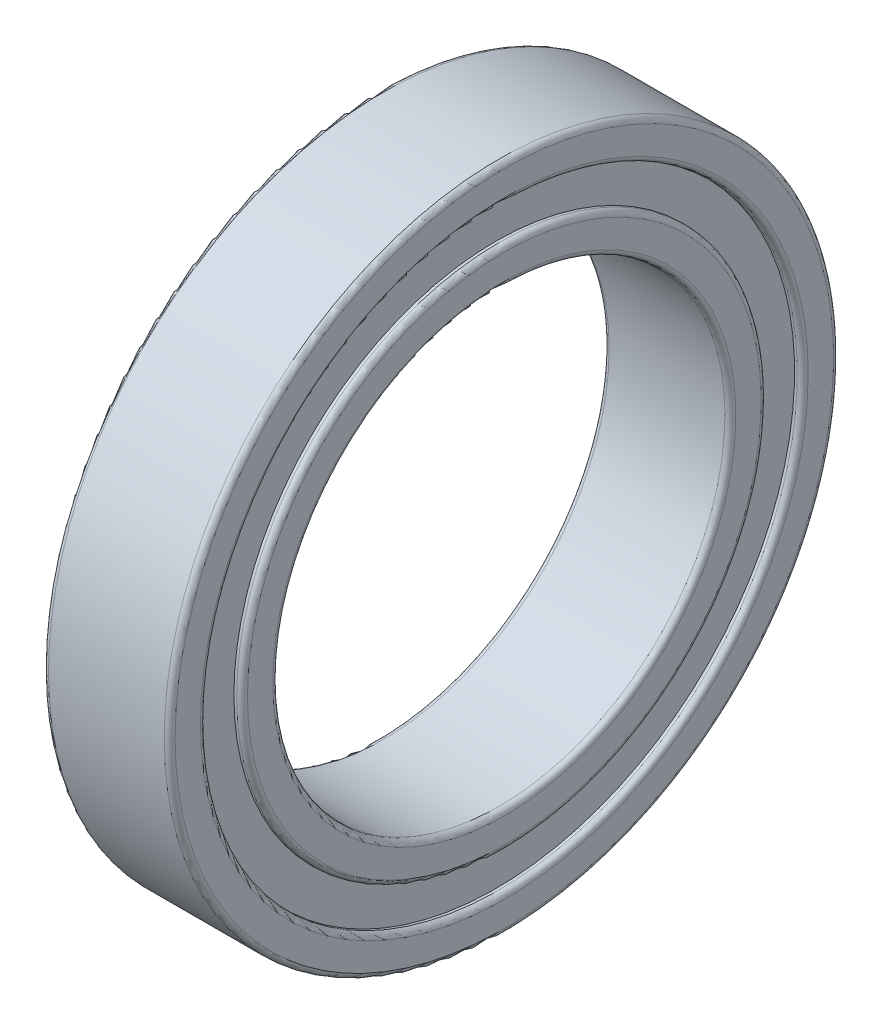
SolidWorks part; units mm, degrees
material "AISI 304"
ref_plane "前视基准面" through (0, 0, 0) normal (0, 0, 1) x (1, 0, 0)
ref_plane "上视基准面" through (0, 0, 0) normal (0, 1, 0) x (1, 0, 0)
ref_plane "右视基准面" through (0, 0, 0) normal (1, 0, 0) x (0, 0, -1)
sketch "尺寸草图" plane through (0, 0, 0) normal (0, 0, 1) x (1, 0, 0)
  line L0 (-19.9271, 0) -> (19.9271, 0) construction
  line L1 (0, 21.603) -> (0, -21.603) construction
  line L2 (-3.2, 18.5) -> (3.2, 18.5)
  line L3 (3.5, 18.2) -> (3.5, 16.8)
  line L4 (-3.5, 18.2) -> (-3.5, 16.8)
  line L5 (-3.2, 16.5) -> (3.2, 16.5)
  line L6 (-3.5, 15.5) -> (3.3577, 15.5) construction
  line L7 (-3.2, 14.5) -> (3.2, 14.5)
  line L8 (3.5, 14.2) -> (3.5, 12.8)
  line L9 (3.2, 12.5) -> (-3.2, 12.5)
  line L10 (-3.5, 12.8) -> (-3.5, 14.2)
  line L11 (0, 15.5) -> (0, 17) construction
  line L13 (2.75, 16.8) -> (3.05, 16.8)
  line L14 (2.75, 16.8) -> (2.75, 14.2)
  line L15 (2.75, 14.2) -> (3.05, 14.2)
  line L16 (3.05, 16.8) -> (3.05, 14.2)
  circle A0 centre (0, 15.5) radius 1.5
  arc A1 (3.5, 16.8) -> (3.2, 16.5) centre (3.2, 16.8) cw
  arc A2 (3.5, 14.2) -> (3.2, 14.5) centre (3.2, 14.2) ccw
  arc A3 (-3.2, 14.5) -> (-3.5, 14.2) centre (-3.2, 14.2) ccw
  arc A4 (-3.2, 16.5) -> (-3.5, 16.8) centre (-3.2, 16.8) cw
  arc A5 (-3.2, 12.5) -> (-3.5, 12.8) centre (-3.2, 12.8) cw
  arc A6 (3.2, 12.5) -> (3.5, 12.8) centre (3.2, 12.8) ccw
  arc A7 (3.5, 18.2) -> (3.2, 18.5) centre (3.2, 18.2) ccw
  arc A8 (-3.2, 18.5) -> (-3.5, 18.2) centre (-3.2, 18.2) ccw
  point P7 (0, 0)
  point P25 (-3.5, 14.5)
  point P28 (-3.5, 16.5)
  point P31 (-3.5, 12.5)
  point P36 (3.5, 18.5)
  point P39 (-3.5, 18.5)
  dimension "D1" = 0.5
  dimension "D3" = 0.3
  dimension "D4" = 0.45
  dimension "B" = 7
  dimension "D2" = 3.5
  dimension "D" = 37
  dimension "(d)" = 25
  dimension "D5" = 15.5
  dimension "D6" = 2
  dimension "D7" = 2
  dimension "D8" = 0.3
  dimension "D10" = 0.3
sketch "草图2" plane through (0, 0, 0) normal (0, 0, 1) x (1, 0, 0)
  line L6 (3.2, 12.5) -> (-3.2, 12.5) construction
  line L8 (-3.5, 18.2) -> (-3.5, 16.8) construction
  line L9 (-3.2, 16.5) -> (3.2, 16.5) construction
  line L10 (-3.2, 18.5) -> (3.2, 18.5) construction
  line L11 (3.5, 18.2) -> (3.5, 16.8) construction
  line L12 (3.5, 14.2) -> (3.5, 12.8) construction
  line L13 (-3.2, 14.5) -> (3.2, 14.5) construction
  line L14 (3.2, 12.5) -> (-3.2, 12.5)
  line L15 (-3.5, 12.8) -> (-3.5, 14.2) construction
  line L18 (-3.5, 0) -> (3.5, 0) construction
  line L19 (-19.9271, 0) -> (19.9271, 0) construction
  line L20 (-3.5, 18.2) -> (-3.5, 16.8)
  line L21 (-3.2, 16.5) -> (-1.118, 16.5)
  line L22 (-3.2, 18.5) -> (3.2, 18.5)
  line L23 (3.5, 18.2) -> (3.5, 16.8)
  line L24 (3.5, 14.2) -> (3.5, 12.8)
  line L25 (-3.2, 14.5) -> (-1.118, 14.5)
  line L26 (-3.5, 12.8) -> (-3.5, 14.2)
  line L27 (1.118, 16.5) -> (3.2, 16.5)
  line L28 (1.118, 14.5) -> (3.2, 14.5)
  circle A0 centre (0, 15.5) radius 1.5 construction
  arc A1 (1.118, 16.5) -> (-1.118, 16.5) centre (0, 15.5) ccw
  arc A2 (-1.118, 14.5) -> (1.118, 14.5) centre (0, 15.5) ccw
  arc A3 (-3.2, 18.5) -> (-3.5, 18.2) centre (-3.2, 18.2) ccw construction
  arc A4 (-3.5, 16.8) -> (-3.2, 16.5) centre (-3.2, 16.8) ccw construction
  arc A5 (3.5, 18.2) -> (3.2, 18.5) centre (3.2, 18.2) ccw construction
  arc A6 (3.2, 16.5) -> (3.5, 16.8) centre (3.2, 16.8) ccw construction
  arc A7 (3.5, 14.2) -> (3.2, 14.5) centre (3.2, 14.2) ccw construction
  arc A8 (3.2, 12.5) -> (3.5, 12.8) centre (3.2, 12.8) ccw construction
  arc A9 (-3.2, 14.5) -> (-3.5, 14.2) centre (-3.2, 14.2) ccw construction
  arc A10 (-3.5, 12.8) -> (-3.2, 12.5) centre (-3.2, 12.8) ccw construction
  arc A11 (-3.2, 18.5) -> (-3.5, 18.2) centre (-3.2, 18.2) ccw
  arc A12 (-3.5, 16.8) -> (-3.2, 16.5) centre (-3.2, 16.8) ccw
  arc A13 (3.5, 18.2) -> (3.2, 18.5) centre (3.2, 18.2) ccw
  arc A14 (3.2, 16.5) -> (3.5, 16.8) centre (3.2, 16.8) ccw
  arc A15 (3.5, 14.2) -> (3.2, 14.5) centre (3.2, 14.2) ccw
  arc A16 (3.2, 12.5) -> (3.5, 12.8) centre (3.2, 12.8) ccw
  arc A17 (-3.2, 14.5) -> (-3.5, 14.2) centre (-3.2, 14.2) ccw
  arc A18 (-3.5, 12.8) -> (-3.2, 12.5) centre (-3.2, 12.8) ccw
revolve "旋转1" add sketch "草图2" angle 360 about L18
sketch "草图5" plane through (0, 0, 0) normal (0, 0, 1) x (1, 0, 0)
  line L1 (-0.45, 15.2) -> (0.45, 15.2)
  line L2 (-0.45, 15.2) -> (-0.45, 15.8)
  line L3 (-0.45, 15.8) -> (0.45, 15.8)
  line L4 (0.45, 15.2) -> (0.45, 15.8)
  line L5 (-0.45, 15.2) -> (0.45, 15.8) construction
  line L6 (-0.45, 15.8) -> (0.45, 15.2) construction
  circle A0 centre (0, 15.5) radius 1.5 construction
  circle A1 centre (0, 15.5) radius 1.5 construction
  point P0 (0, 15.5)
  dimension "D1" = 0.9
  dimension "D2" = 0.6
revolve "旋转3" add sketch "草图5" angle 360 about L0
sketch "草图3" plane through (0, 0, 0) normal (0, 0, 1) x (1, 0, 0)
  line L1 (-1.65, 15.5) -> (1.65, 15.5)
  circle A0 centre (0, 15.5) radius 1.5 construction
  circle A1 centre (0, 15.5) radius 1.5 construction
  arc A2 (1.65, 15.5) -> (-1.65, 15.5) centre (0, 15.5) ccw
  dimension "D2" = 3.3
revolve "旋转2" add sketch "草图3" angle 360 about L1 region at (0, 16.2003, 0)
ref_axis "基准轴1" through (-13.2, 0, 0) along (1, 0, 0)
pattern_circular "阵列(圆周)5" count 26 over 360 about axis through (-13.2, 0, 0) along (1, 0, 0) of bodies 103
sketch "草图6" plane through (0, 0, 0) normal (0, 0, 1) x (1, 0, 0)
  line L0 (-1.6225, 15.8) -> (1.6225, 15.8)
  line L1 (-3.5, 15.5) -> (3.5, 15.5) construction
  line L3 (-1.6225, 15.2) -> (1.6225, 15.2)
  line L4 (3.5, -18.2) -> (3.5, 18.2) construction
  arc A0 (-1.6225, 15.2) -> (1.6225, 15.2) centre (0, 15.5) ccw
  circle A1 centre (0, 15.5) radius 1.5 construction
  circle A2 centre (0, 15.5) radius 1.5 construction
  arc A3 (1.6225, 15.8) -> (-1.6225, 15.8) centre (0, 15.5) ccw
  dimension "D1" = 3.3
  dimension "D3" = 0.3
  dimension "D4" = 0.3
revolve "切除-旋转1" cut sketch "草图6" angle 360 about L0
sketch "草图7" plane through (0, 0, 0) normal (0, 0, 1) x (1, 0, 0)
  line L0 (-1.5, 15.5) -> (1.5, 15.5)
  line L1 (-3.5, 0) -> (3.5, 0) construction
  line L2 (-3.5, 18.2) -> (-3.5, -18.2) construction
  line L3 (3.5, -18.2) -> (3.5, 18.2) construction
  circle A0 centre (0, 15.5) radius 1.5 construction
  arc A1 (1.5, 15.5) -> (-1.5, 15.5) centre (0, 15.5) ccw
revolve "旋转4" add sketch "草图7" angle 360 about L0
pattern_circular "阵列(圆周)2" count 26 over 360 about axis through (-13.2, 0, 0) along (1, 0, 0) of "旋转4"
sketch "草图8" plane through (0, 0, 0) normal (0, 0, 1) x (1, 0, 0)
  line L0 (2.75, 16.8) -> (2.75, 14.2) construction
  line L1 (3.05, 16.8) -> (3.05, 14.2) construction
  line L2 (2.75, 16.8) -> (3.05, 16.8) construction
  line L3 (2.75, 14.2) -> (3.05, 14.2) construction
  line L4 (2.75, 16.8) -> (2.75, 14.2)
  line L5 (3.05, 16.8) -> (3.05, 14.2)
  line L6 (2.75, 16.8) -> (3.05, 16.8)
  line L7 (2.75, 14.2) -> (3.05, 14.2)
  line L8 (-3.5, 0) -> (3.5, 0) construction
  line L9 (-3.5, 18.2) -> (-3.5, -18.2) construction
  line L10 (3.5, -18.2) -> (3.5, 18.2) construction
  line L11 (0, 18.5) -> (0, 0) construction
  line L12 (-3.2, 18.5) -> (3.2, 18.5) construction
  line L13 (-2.75, 14.2) -> (-3.05, 14.2)
  line L14 (-2.75, 16.8) -> (-3.05, 16.8)
  line L15 (-3.05, 16.8) -> (-3.05, 14.2)
  line L16 (-2.75, 16.8) -> (-2.75, 14.2)
revolve "旋转5" add sketch "草图8" angle 360 about L0
